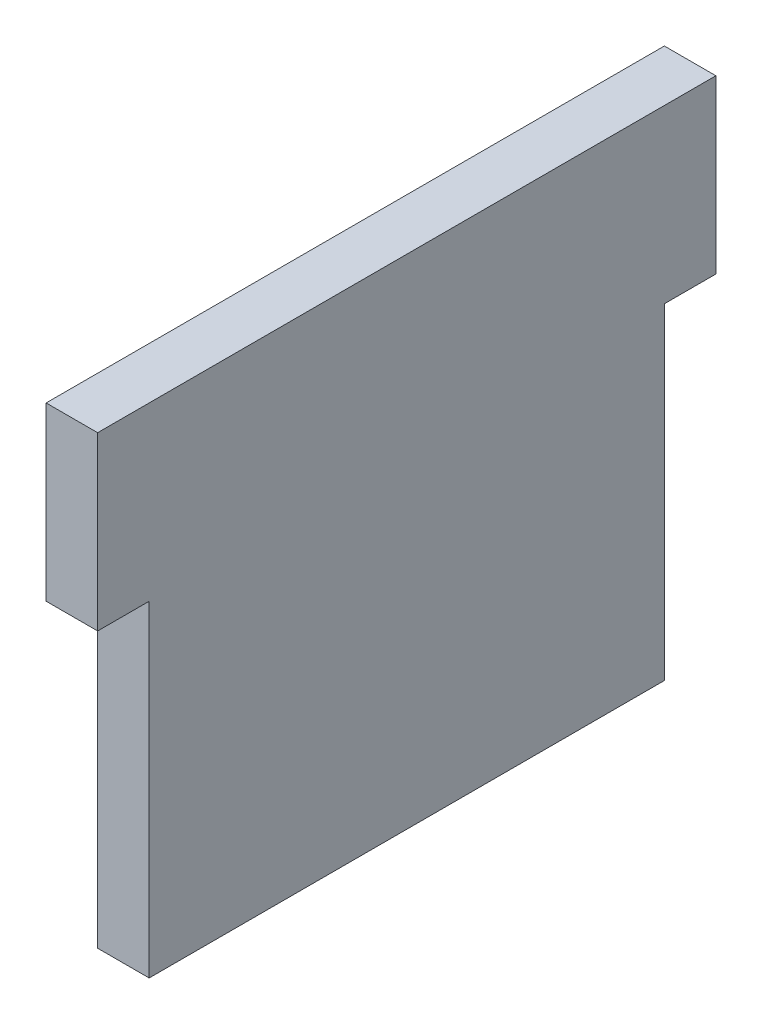
SolidWorks part; units mm, degrees
material "Acrilico TEC"
ref_plane "Front Plane" through (0, 0, 0) normal (0, 0, 1) x (1, 0, 0)
ref_plane "Top Plane" through (0, 0, 0) normal (0, 1, 0) x (1, 0, 0)
ref_plane "Right Plane" through (0, 0, 0) normal (1, 0, 0) x (0, 0, -1)
sketch "Sketch1" plane through (0, 0, 0) normal (1, 0, 0) x (0, 0, -1)
  line L0 (15, 6.47) -> (-15, 6.47)
  line L1 (-18, 25.47) -> (-18, 35.47)
  line L3 (-15, 6.47) -> (-15, 25.47)
  line L4 (18, 25.47) -> (15, 25.47)
  line L6 (15, 35.47) -> (-15, 35.47)
  line L7 (0, 35.47) -> (0, 0) construction
  line L8 (-18, 25.47) -> (-15, 25.47)
  line L10 (-18, 35.47) -> (-15, 35.47)
  line L15 (15, 6.47) -> (15, 25.47)
  line L16 (18, 25.47) -> (18, 35.47)
  line L17 (18, 35.47) -> (15, 35.47)
  dimension "D1" = 19
  dimension "D2" = 3
  dimension "D4" = 10
extrude "Boss-Extrude1" add sketch "Sketch1" along normal blind 3
